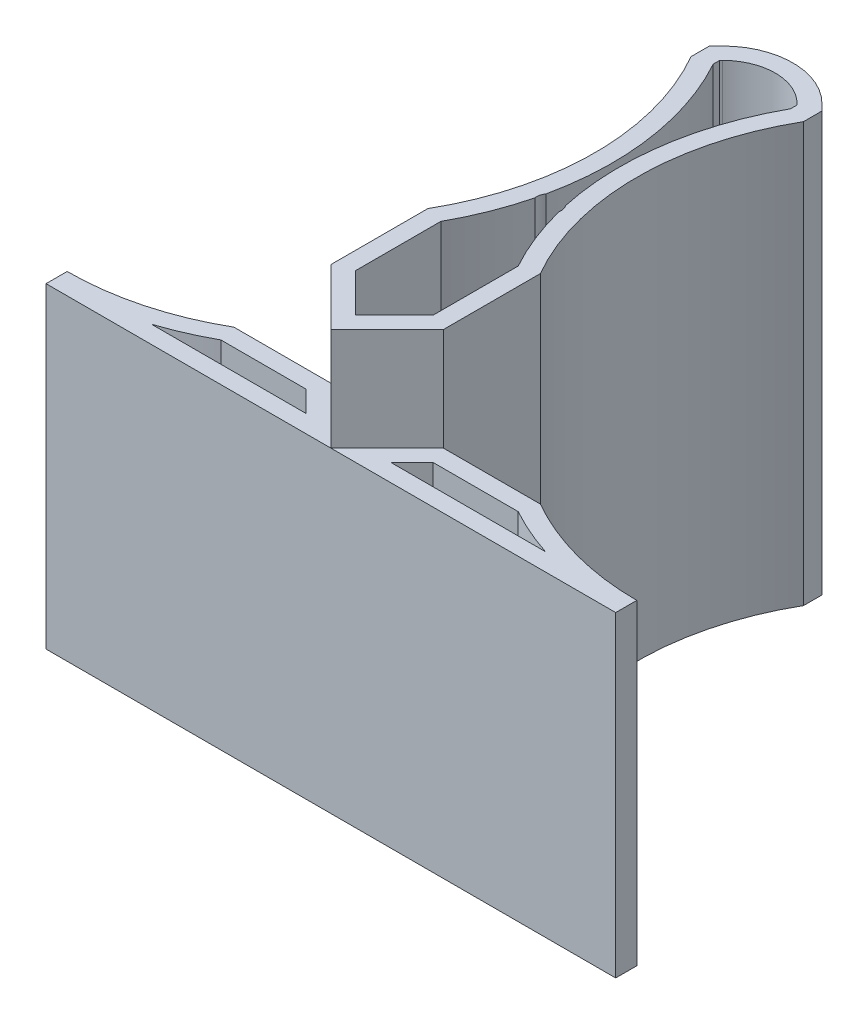
SolidWorks part; units mm, degrees
ref_plane "Front Plane" through (0, 0, 0) normal (0, 0, 1) x (1, 0, 0)
ref_plane "Top Plane" through (0, 0, 0) normal (0, 1, 0) x (1, 0, 0)
ref_plane "Right Plane" through (0, 0, 0) normal (1, 0, 0) x (0, 0, -1)
sketch "Sketch1" plane through (0, 0, 0) normal (0, 1, 0) x (1, 0, 0)
  line L0 (23.7595, 41.275) -> (41.275, 41.275) construction
  line L1 (-41.275, -41.275) -> (-23.7595, -41.275) construction
  line L2 (-41.275, -41.275) -> (-41.275, -23.7595) construction
  line L3 (-41.275, 41.275) -> (-23.7595, 41.275) construction
  line L4 (41.275, -41.275) -> (41.275, -23.7595) construction
  line L5 (-41.275, -41.275) -> (41.275, 41.275) construction
  line L6 (-41.275, 41.275) -> (41.275, -41.275) construction
  line L7 (41.275, 23.7595) -> (41.275, 41.275) construction
  line L8 (-41.275, 23.7595) -> (-41.275, 41.275) construction
  line L9 (23.7595, -41.275) -> (41.275, -41.275) construction
  line L10 (24.7569, 45.085) -> (45.085, 45.085) construction
  line L11 (45.085, 24.7569) -> (45.085, 45.085) construction
  line L12 (45.085, -45.085) -> (45.085, -24.7569) construction
  line L13 (24.7569, -45.085) -> (45.085, -45.085) construction
  line L14 (-45.085, -45.085) -> (-24.7569, -45.085) construction
  line L15 (-45.085, -45.085) -> (-45.085, -24.7569) construction
  line L16 (-45.085, 24.7569) -> (-45.085, 45.085) construction
  line L17 (-45.085, 45.085) -> (-24.7569, 45.085) construction
  line L19 (-51.435, -51.435) -> (51.435, -51.435) construction
  line L20 (-51.435, -51.435) -> (-51.435, 51.435) construction
  line L21 (-51.435, 51.435) -> (51.435, 51.435) construction
  line L22 (51.435, -51.435) -> (51.435, 51.435) construction
  line L23 (-51.435, -51.435) -> (51.435, 51.435) construction
  line L24 (-51.435, 51.435) -> (51.435, -51.435) construction
  arc A1 (-41.275, 23.7595) -> (-41.275, -23.7595) centre (0, 0) ccw construction
  arc A2 (23.7595, 41.275) -> (-23.7595, 41.275) centre (0, 0) ccw construction
  arc A3 (-23.7595, -41.275) -> (23.7595, -41.275) centre (0, 0) ccw construction
  arc A4 (41.275, -23.7595) -> (41.275, 23.7595) centre (0, 0) ccw construction
  arc A5 (45.085, -24.7569) -> (45.085, 24.7569) centre (0, 0) ccw construction
  arc A6 (-24.7569, -45.085) -> (24.7569, -45.085) centre (0, 0) ccw construction
  arc A7 (-45.085, 24.7569) -> (-45.085, -24.7569) centre (0, 0) ccw construction
  arc A8 (24.7569, 45.085) -> (-24.7569, 45.085) centre (0, 0) ccw construction
  point P0 (0, 0)
  dimension "D1" = 82.55
  dimension "D2" = 82.55
  dimension "D3" = 95.25
  dimension "D4" = 3.81
sketch "Sketch2" plane through (0, 0, 0) normal (0, 0, 1) x (1, 0, 0)
  line L0 (0, 48) -> (0, 0) construction
  line L1 (0, 0) -> (0, -9.15) construction
  line L2 (0, 48) -> (0, 66.542) construction
  point P3 (0, 0)
  point P6 (0, 0)
  point P7 (0, 0)
  point P8 (0, 0)
  point P9 (0, 0)
  point P10 (0, 0)
  point P11 (0, 0)
  dimension "Cage height" = 48
  dimension "Plate height" = 18.542
  dimension "D1" = 57.15
  dimension "D2" = 9.15
sketch "Sketch13" plane through (0, 0, 0) normal (0, 1, 0) x (1, 0, 0)
  line L0 (-51.435, -51.435) -> (51.435, -51.435) construction
  line L1 (-41.275, -41.275) -> (-23.7595, -41.275) construction
  line L2 (-41.275, -41.275) -> (-41.275, -23.7595) construction
  line L4 (-51.435, -51.435) -> (0, -51.435)
  line L5 (-41.275, -41.275) -> (-23.7595, -41.275)
  line L6 (-41.275, -41.275) -> (-41.275, -23.7595)
  line L9 (0, -47.625) -> (0, -51.435)
  line L10 (-51.435, 51.435) -> (51.435, -51.435) construction
  line L11 (-41.275, 23.7595) -> (-41.275, 41.275) construction
  line L12 (-51.435, -51.435) -> (-51.435, 51.435) construction
  line L13 (-51.435, 51.435) -> (-41.275, 41.275)
  line L14 (-41.275, 23.7595) -> (-41.275, 41.275)
  line L15 (-51.435, -51.435) -> (-51.435, 51.435)
  arc A0 (-23.7595, -41.275) -> (23.7595, -41.275) centre (0, 0) ccw construction
  arc A2 (-23.7595, -41.275) -> (0, -47.625) centre (0, 0) ccw
  arc A4 (-41.275, 23.7595) -> (-41.275, -23.7595) centre (0, 0) ccw construction
  arc A5 (-41.275, 23.7595) -> (-41.275, -23.7595) centre (0, 0) ccw
  point P3 (0, -47.625)
  point P5 (-23.7595, -41.275)
  point P14 (-41.275, -41.275)
  point P18 (0, -51.435)
  point P19 (0, -47.625)
  point P20 (0, -51.435)
  point P21 (-51.435, -2.0895)
  point P22 (-47.625, 0)
extrude "Boss-Extrude2" add sketch "Sketch13" along normal up to vertex (66.542 mm away) and the other way up to vertex (9.15 mm away) up to point (0, 66.542, 0) other way up to point (0, -9.15, 0)
sketch "Sketch15" plane through (0, 66.542, 0) normal (0, 1, 0) x (1, 0, 0)
  line L0 (0, 0) -> (-51.435, -51.435)
  line L1 (-51.435, -51.435) -> (0, -51.435)
  line L2 (0, -51.435) -> (0, 0)
  line L3 (-51.435, -51.435) -> (51.435, -51.435) construction
  point P4 (0, 0)
  point P7 (-42.7508, -51.435)
extrude "Cut-Extrude2" cut sketch "Sketch15" against normal up to vertex (18.542 mm away) up to point (0, 48, 0)
mirror "Mirror1" about plane through (-51.435, 66.542, 51.435) normal (1, 0, 0) of "Boss-Extrude2", "Cut-Extrude2"
sketch "Sketch16" plane through (0, -9.15, 0) normal (0, -1, 0) x (1, 0, 0)
  line L0 (-51.435, 51.435) -> (-51.435, -51.435) construction
  line L1 (-102.87, 51.435) -> (0, 51.435) construction
  line L2 (-51.435, 51.435) -> (-51.435, -51.435) construction
  circle A0 centre (-70.485, 46.355) radius 2
  circle A1 centre (-51.435, 25.4) radius 2
  circle A3 centre (-32.385, 46.355) radius 2
  circle A5 centre (-51.435, -25.4) radius 2
  point P13 (0, 0)
  dimension "D1" = 4
  dimension "D2" = 19.05
  dimension "D3" = 5.08
  dimension "D4" = 25.4
  dimension "D6" = 25.4
extrude "Cut-Extrude3" cut sketch "Sketch16" against normal blind 31.75
sketch "Sketch17" plane through (0, 66.542, 0) normal (0, 1, 0) x (1, 0, 0)
  line L0 (7.0944, 7.0944) -> (-7.0944, -7.0944)
  line L1 (7.0944, 7.0944) -> (-44.3406, 58.5294)
  line L2 (-7.0944, -7.0944) -> (-51.435, 37.2462)
  line L3 (-44.3406, 58.5294) -> (-51.435, 51.435)
  line L4 (-41.275, -41.275) -> (41.275, 41.275) construction
  line L5 (-61.595, 41.275) -> (-51.435, 51.435) construction
  line L6 (-51.435, -51.435) -> (-51.435, 51.435) construction
  line L7 (-51.435, 7.7321) -> (-51.435, 82.5591) construction
  line L8 (-95.7756, -7.0944) -> (-51.435, 37.2462)
  line L9 (-58.5294, 58.5294) -> (-51.435, 51.435)
  line L10 (-109.9644, 7.0944) -> (-58.5294, 58.5294)
  line L11 (-109.9644, 7.0944) -> (-95.7756, -7.0944)
  dimension "D1" = 20.066
extrude "Cut-Extrude4" cut sketch "Sketch17" against normal through all
fillet "Fillet2" radius 12.7 1 edges at (-51.435, 28.696, -37.2462)
sketch "Sketch18" plane through (0, 66.542, 0) normal (0, 1, 0) x (1, 0, 0)
  line L19 (-58.42, -24.5934) -> (-58.42, -39.9599)
  line L20 (-58.42, -39.9599) -> (-51.435, -46.9449)
  line L21 (-51.435, -46.9449) -> (-44.45, -39.9599)
  line L22 (-44.45, -39.9599) -> (-44.45, -24.5934)
  line L27 (-58.42, -24.5934) -> (-58.42, -39.9599)
  line L28 (-58.42, -39.9599) -> (-51.435, -46.9449)
  line L29 (-51.435, -46.9449) -> (-44.45, -39.9599)
  line L30 (-44.45, -39.9599) -> (-44.45, -24.5934)
  line L32 (-62.9101, -44.45) -> (-78.2766, -44.45)
  line L33 (-87.0077, -48.26) -> (-59.1001, -48.26)
  line L34 (-59.1001, -48.26) -> (-62.9101, -44.45)
  line L35 (-62.9101, -44.45) -> (-78.2766, -44.45)
  line L36 (-87.0077, -48.26) -> (-59.1001, -48.26)
  line L37 (-59.1001, -48.26) -> (-62.9101, -44.45)
  line L42 (-24.5934, -44.45) -> (-39.9599, -44.45)
  line L43 (-39.9599, -44.45) -> (-43.7699, -48.26)
  line L44 (-43.7699, -48.26) -> (-15.8623, -48.26)
  line L45 (-24.5934, -44.45) -> (-39.9599, -44.45)
  line L46 (-39.9599, -44.45) -> (-43.7699, -48.26)
  line L47 (-43.7699, -48.26) -> (-15.8623, -48.26)
  line L48 (-44.45, 25.7711) -> (-44.6998, 26.0209)
  line L49 (-44.45, 25.7711) -> (-44.6998, 26.0209)
  line L50 (-58.1702, 26.0209) -> (-58.42, 25.7711)
  line L51 (-58.1702, 26.0209) -> (-58.42, 25.7711)
  line L52 (-58.42, 25.7711) -> (-58.42, 24.5934)
  line L53 (-58.42, 25.7711) -> (-58.42, 24.5934)
  line L54 (-44.45, 24.5934) -> (-44.45, 25.7711)
  line L55 (-44.45, 24.5934) -> (-44.45, 25.7711)
  arc A5 (-87.0077, -48.26) -> (-78.2766, -44.45) centre (-102.87, 0) ccw
  arc A6 (-44.6998, 26.0209) -> (-58.1702, 26.0209) centre (-51.435, 19.2857) ccw
  arc A7 (-58.42, -24.5934) -> (-58.42, 24.5934) centre (-102.87, 0) ccw
  arc A8 (-44.45, 24.5934) -> (-44.45, -24.5934) centre (0, 0) ccw
  arc A9 (-44.6998, 26.0209) -> (-58.1702, 26.0209) centre (-51.435, 19.2857) ccw
  arc A10 (-58.42, -24.5934) -> (-58.42, 24.5934) centre (-102.87, 0) ccw
  arc A11 (-44.45, 24.5934) -> (-44.45, -24.5934) centre (0, 0) ccw
  arc A12 (-87.0077, -48.26) -> (-78.2766, -44.45) centre (-102.87, 0) ccw
  arc A14 (-24.5934, -44.45) -> (-15.8623, -48.26) centre (0, 0) ccw
  arc A15 (-24.5934, -44.45) -> (-15.8623, -48.26) centre (0, 0) ccw
  dimension "D1" = 3.175
  dimension "D2" = 3.175
  dimension "D3" = 3.175
extrude "Cut-Extrude5" cut sketch "Sketch18" against normal up to surface (43.942 mm away) up to face at (-51.435, 22.6, -27.4)
sketch "Sketch20" plane through (0, 22.6, 0) normal (0, 1, 0) x (1, 0, 0)
  line L0 (-58.42, -31.75) -> (-44.45, -31.75)
  line L2 (-47.0929, 19.05) -> (-55.7771, 19.05)
  line L3 (-55.7771, -19.05) -> (-47.0929, -19.05)
  line L12 (-58.42, -24.5934) -> (-58.42, -39.9599)
  line L13 (-58.42, -39.9599) -> (-51.435, -46.9449)
  line L14 (-51.435, -46.9449) -> (-44.45, -39.9599)
  line L15 (-44.45, -39.9599) -> (-44.45, -24.5934)
  line L20 (-58.42, -31.75) -> (-58.42, -39.9599)
  line L21 (-58.42, -39.9599) -> (-51.435, -46.9449)
  line L22 (-51.435, -46.9449) -> (-44.45, -39.9599)
  line L23 (-44.45, -39.9599) -> (-44.45, -31.75)
  line L25 (-44.45, 24.5934) -> (-44.45, 25.7711)
  line L26 (-44.45, 25.7711) -> (-44.6998, 26.0209)
  line L27 (-58.1702, 26.0209) -> (-58.42, 25.7711)
  line L28 (-58.42, 25.7711) -> (-58.42, 24.5934)
  circle A0 centre (-51.435, -25.4) radius 2 construction
  circle A1 centre (-51.435, 25.4) radius 2 construction
  arc A4 (-58.42, -24.5934) -> (-58.42, 24.5934) centre (-102.87, 0) ccw
  arc A5 (-44.45, 24.5934) -> (-44.45, -24.5934) centre (0, 0) ccw
  arc A7 (-55.7771, -19.05) -> (-55.7771, 19.05) centre (-102.87, 0) ccw
  arc A8 (-47.0929, 19.05) -> (-47.0929, -19.05) centre (0, 0) ccw
  arc A11 (-44.6998, 26.0209) -> (-58.1702, 26.0209) centre (-51.435, 19.2857) ccw
  point P22 (0, 0)
  point P23 (0, 0)
  dimension "D2" = 6.35
  dimension "D5" = 6.35
  dimension "D3" = 6.35
  dimension "D1" = 0
extrude "Cut-Extrude6" cut sketch "Sketch20" against normal through all
sketch "Sketch21" plane through (0, -9.15, 0) normal (0, 1, 0) x (1, 0, 0)
  circle A0 centre (-51.435, 25.4) radius 2 construction
  circle A1 centre (-51.435, -25.4) radius 2 construction
  circle A2 centre (-32.385, -46.355) radius 2 construction
  circle A3 centre (-70.485, -46.355) radius 2 construction
  circle A4 centre (-51.435, 25.4) radius 2 construction
  circle A5 centre (-51.435, -25.4) radius 2 construction
  circle A6 centre (-32.385, -46.355) radius 2 construction
  circle A7 centre (-70.485, -46.355) radius 2 construction
sketch "Sketch22" plane through (0, 0, 0) normal (0, 1, 0) x (1, 0, 0)
  line L0 (-51.435, -51.435) -> (-51.435, 51.435) construction
  line L1 (-51.435, 51.435) -> (51.435, 51.435) construction
  circle A0 centre (-51.435, -12.065) radius 2.2
  dimension "D1" = 4.4
  dimension "D2" = 63.5
extrude "Cut-Extrude7" cut sketch "Sketch22" against normal through all both and the other way through all
equation "\"tightTol\"= 0.005in"
equation "\"normTol\"= 0.01in"
equation "\"looseTol\"= 0.02in"
equation "\"Cage height@Sketch2\"=48mm"
equation "\"Plate height@Sketch2\"= 0.750000in - \"looseTol\""
equation "\"D1@Sketch16\"=4mm"
equation "\"D1@Sketch17\"=0.75in+2*\"looseTol\""
equation "\"D1@Sketch22\"=4.4mm"
